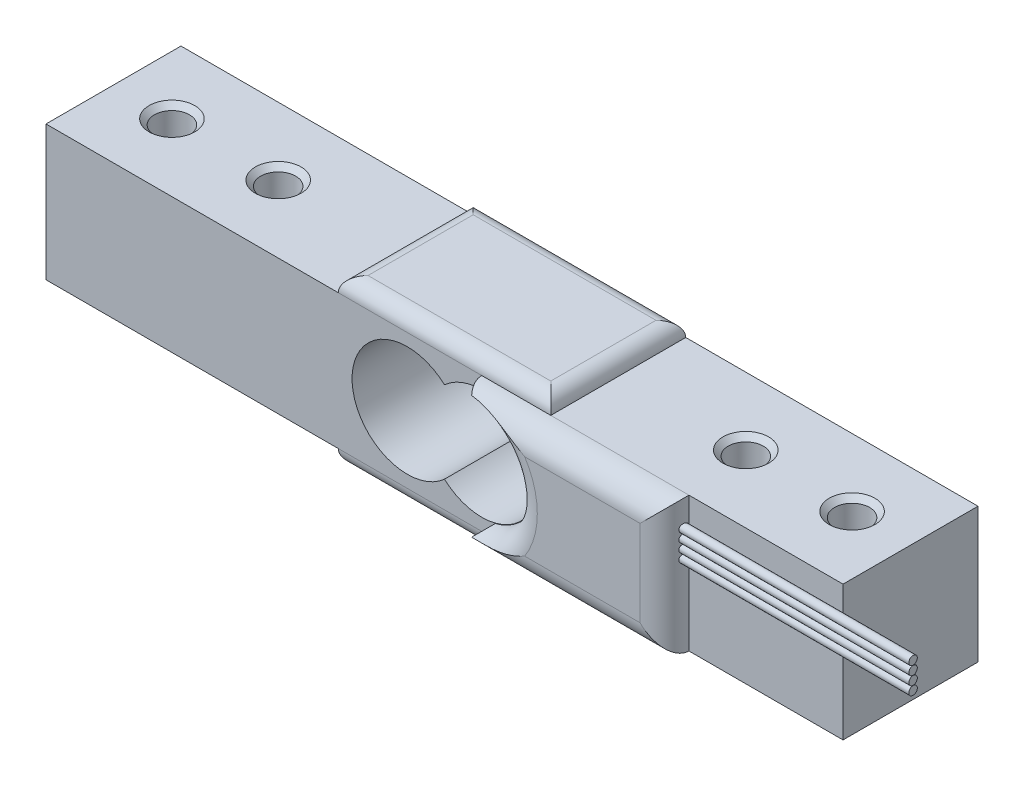
SolidWorks part; units mm, degrees
ref_plane "前视基准面" through (0, 0, 0) normal (0, 0, 1) x (1, 0, 0)
ref_plane "上视基准面" through (0, 0, 0) normal (0, 1, 0) x (1, 0, 0)
ref_plane "右视基准面" through (0, 0, 0) normal (1, 0, 0) x (0, 0, -1)
sketch "草图1" plane through (0, 0, 0) normal (0, 0, 1) x (1, 0, 0)
  line L1 (-37.5, 6.35) -> (37.5, 6.35)
  line L2 (-37.5, 6.35) -> (-37.5, -6.35)
  line L3 (-37.5, -6.35) -> (37.5, -6.35)
  line L4 (37.5, 6.35) -> (37.5, -6.35)
  line L5 (-37.5, 6.35) -> (37.5, -6.35) construction
  line L6 (-37.5, -6.35) -> (37.5, 6.35) construction
  arc A0 (0, 3.8458) -> (0, -3.8458) centre (-3.5, 0) ccw
  arc A2 (0, -3.8458) -> (0, 3.8458) centre (3.5, 0) ccw
  point P0 (0, 0)
  dimension "D1" = 12.7
  dimension "D2" = 75
extrude "凸台-拉伸1" add sketch "草图1" along normal mid plane 12.7
sketch "草图2" plane through (0, 6.35, 0) normal (0, 1, 0) x (1, 0, 0)
  point P0 (-32, 0)
  point P4 (0, 0)
  point P6 (32, 0)
  point P7 (-32, 0)
  point P8 (-22, 0)
  point P9 (22, 0)
hole_wizard "M4 螺纹孔1" positions "3D草图1" profile "草图3" tap size "M4" standard "GB" end condition through all
sketch3d "3D草图1"
  point P0 (-32, 6.35, 0)
  point P3 (-22, 6.35, 0)
  point P6 (22, 6.35, 0)
  point P9 (32, 6.35, 0)
sketch "草图3" plane through (-32, 6.35, 0) normal (1, 0, 0) x (0, 0, 1)
  line L0 (0, 0) -> (0, 12.7)
  line L1 (0, 12.7) -> (1.65, 12.7)
  line L2 (1.65, 12.7) -> (1.65, 0)
  line L5 (1.65, 0) -> (0, 0)
  line L11 (0, -6.35) -> (0, 107.95) construction
  dimension "通孔螺纹孔钻头直径" = 3.3
  dimension "通孔螺纹孔钻头深度" = 12.7
cosmetic thread "孔螺蚊线1" parameters "D2"=4
cosmetic thread "孔螺蚊线2" parameters "D2"=4
cosmetic thread "孔螺蚊线3" parameters "D2"=4
cosmetic thread "孔螺蚊线4" parameters "D2"=4
chamfer "倒角1" distance 0.5 angle 45 8 edges at (32, -6.35, 1.65) (22, -6.35, 1.65) (-32, -6.35, 1.65) (-22, -6.35, 1.65) (32, 6.35, 1.65) (22, 6.35, 1.65) (-22, 6.35, 1.65) (-32, 6.35, 1.65)
sketch "草图5" plane through (0, 0, 6.35) normal (0, 0, 1) x (1, 0, 0)
  line L0 (-10, 6.35) -> (10, 6.35)
  line L1 (37.5, 6.35) -> (-37.5, 6.35) construction
  line L2 (10, 6.35) -> (10, 7.75)
  line L3 (10, 7.75) -> (-10, 7.75)
  line L4 (-10, 7.75) -> (-10, 6.35)
  point P5 (0, 6.35)
  dimension "D1" = 1.4
extrude "凸台-拉伸2" add sketch "草图5" against normal blind 12.7 separate body
fillet "圆角1" radius 1.4 4 edges at (-10, 7.75, 0) (0, 7.75, -6.35) (10, 7.75, 0) (0, 7.75, 6.35)
mirror "镜向1" about plane through (0, 0, 0) normal (0, 1, 0) of bodies 108
sketch "草图6" plane through (0, 0, 6.35) normal (0, 0, 1) x (1, 0, 0)
  line L0 (23, 6.35) -> (23, -6.35)
  line L1 (37.5, 6.35) -> (-37.5, 6.35) construction
  line L2 (-37.5, -6.35) -> (37.5, -6.35) construction
  line L4 (23, 6.35) -> (3.5, 6.35)
  line L5 (-10, 6.35) -> (10, 6.35) construction
  line L6 (3.5, 6.35) -> (4.7766, 5.0734)
  line L7 (23, -6.35) -> (3.5, -6.35)
  line L11 (3.5, -6.35) -> (4.7766, -5.0734)
  arc A0 (4.7766, -5.0734) -> (4.7766, 5.0734) centre (3.5, 0) ccw
extrude "凸台-拉伸3" add sketch "草图6" along normal blind 2.3 separate body
fillet "圆角2" radius 2.3 4 edges at (23, 0, 8.65) (13.25, -6.35, 8.65) (8.7316, 0, 8.65) (13.25, 6.35, 8.65)
ref_plane "基准面1" through (19.5, 0, 0) normal (1, 0, 0) x (0, 0, -1)
sketch "草图7" plane through (19.5, 0, 0) normal (1, 0, 0) x (0, 0, -1)
  circle A0 centre (-6.76, 3.85) radius 0.4
  circle A1 centre (-6.76, 3.03) radius 0.4
  circle A2 centre (-6.76, 2.21) radius 0.4
  circle A3 centre (-6.76, 1.39) radius 0.4
extrude "凸台-拉伸4" add sketch "草图7" along normal blind 25
sketch "草图8" plane through (0, 0, 6.35) normal (0, 0, 1) x (1, 0, 0)
  line L0 (84.1374, 241.01) -> (558.1374, 241.01) construction
